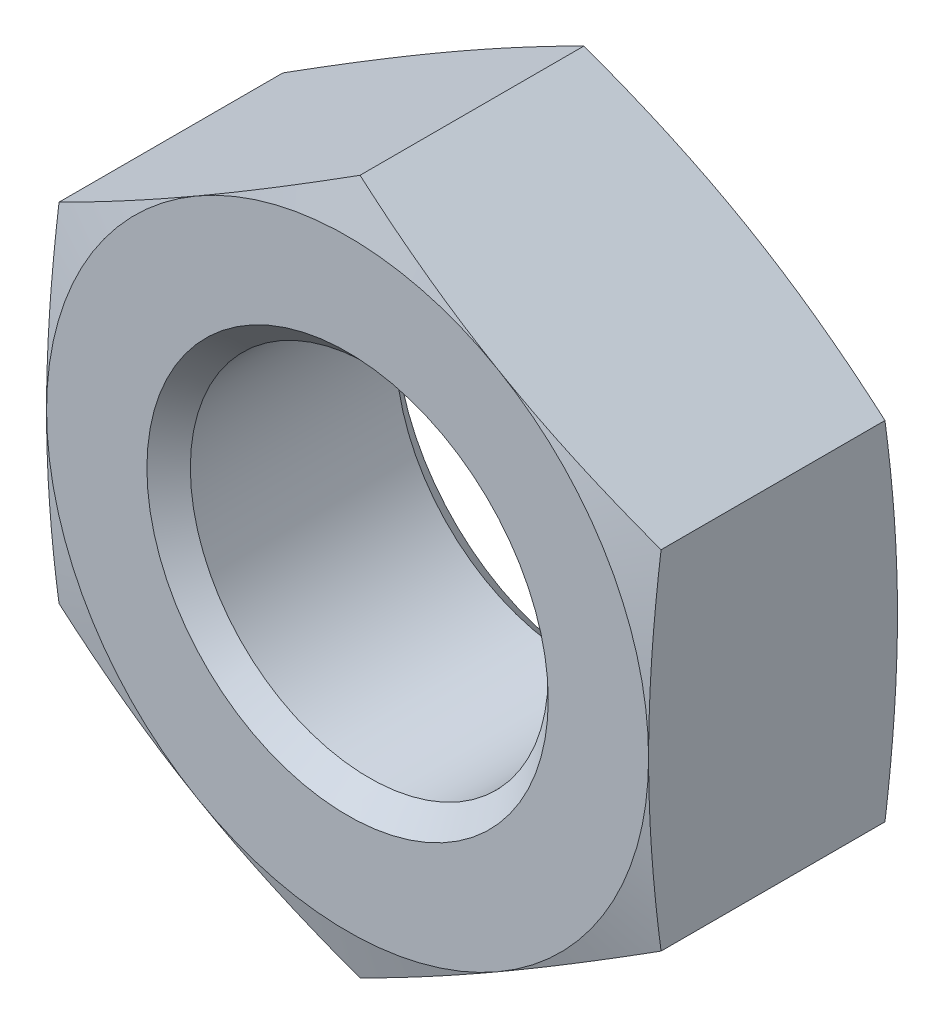
SolidWorks part; units mm, degrees
material "AISI 1045 Steel, cold drawn"
ref_plane "Front Plane" through (0, 0, 0) normal (0, 0, 1) x (1, 0, 0)
ref_plane "Top Plane" through (0, 0, 0) normal (0, 1, 0) x (1, 0, 0)
ref_plane "Right Plane" through (0, 0, 0) normal (1, 0, 0) x (0, 0, -1)
sketch "Sketch1" plane through (0, 0, 0) normal (1, 0, 0) x (0, 0, -1)
  line L0 (0, 0) -> (0, 9.525)
  line L1 (0, 9.525) -> (0.5104, 11.43)
  line L2 (0.5104, 11.43) -> (7.3636, 11.43)
  line L3 (7.3636, 11.43) -> (7.874, 9.525)
  line L4 (7.874, 9.525) -> (7.874, 0)
  line L5 (7.874, 0) -> (0, 0)
  line L6 (7.874, 0) -> (0, 0) construction
sketch "Sketch2" plane through (0, 0, 0) normal (0, 0, 1) x (1, 0, 0)
  line L0 (-19.05, 19.05) -> (-19.05, -19.05)
  line L1 (-19.05, -19.05) -> (19.05, -19.05)
  line L2 (19.05, -19.05) -> (19.05, 19.05)
  line L3 (19.05, 19.05) -> (-19.05, 19.05)
  line L4 (-9.525, 5.4993) -> (-9.525, -5.4993)
  line L5 (-9.525, -5.4993) -> (0, -10.9985)
  line L6 (0, -10.9985) -> (9.525, -5.4993)
  line L7 (9.525, -5.4993) -> (9.525, 5.4993)
  line L8 (9.525, 5.4993) -> (0, 10.9985)
  line L9 (0, 10.9985) -> (-9.525, 5.4993)
revolve "Revolve1" add sketch "Sketch1" angle 360 about L6 reverse direction yes
extrude "Cut-Extrude1" cut sketch "Sketch2" against normal blind 7.874
sketch "Sketch3" plane through (0, 0, 0) normal (1, 0, 0) x (0, 0, -1)
  line L0 (0, 0) -> (0, 6.35)
  line L1 (0, 6.35) -> (0.6871, 5.6629)
  line L2 (0.6871, 5.6629) -> (7.1869, 5.6629)
  line L3 (7.1869, 5.6629) -> (7.874, 6.35)
  line L4 (7.874, 6.35) -> (7.874, 0)
  line L5 (7.874, 0) -> (0, 0)
  line L6 (7.874, 0) -> (0, 0) construction
revolve "Cut-Revolve1" cut sketch "Sketch3" angle 360 about L6 reverse direction yes
cosmetic thread "Cosmetic Thread1" parameters "D1"=7.874, "D2"=12.7
ref_plane "NUT XY" through (0, 0, 0) normal (0, 0, 1) x (1, 0, 0)
ref_plane "NUT XZ" through (0, 0, 0) normal (0, -1, 0) x (-1, 0, 0)
ref_plane "NUT YZ" through (0, 0, 0) normal (1, 0, 0) x (0, 0, -1)
ref_axis "NUT X" through (-80.9, 0, 0) along (1, 0, 0)
ref_axis "NUT Y" through (0, -50, 0) along (0, 1, 0)
ref_axis "NUT Z" through (0, 0, 80.9) along (0, 0, -1)
sketch3d "NUT"
  point P0 (0, 0, 0)
ref_plane "a1 XY" through (0, 0, 0) normal (0, 0, 1) x (1, 0, 0)
ref_plane "a1 XZ" through (0, 9.525, 0) normal (0, -1, 0) x (-1, 0, 0)
ref_plane "a1 YZ" through (-9.525, 0, 0) normal (1, 0, 0) x (0, 0, -1)
ref_axis "a1 X" through (-80.9, 9.525, 0) along (1, 0, 0)
ref_axis "a1 Y" through (-9.525, -50, 0) along (0, 1, 0)
ref_axis "a1 Z" through (-9.525, 9.525, 80.9) along (0, 0, -1)
sketch3d "a1"
  point P0 (-9.525, 9.525, 0)
ref_plane "a2 XY" through (0, 0, 0) normal (0, 0, 1) x (1, 0, 0)
ref_plane "a2 XZ" through (0, 9.525, 0) normal (0, -1, 0) x (-1, 0, 0)
ref_plane "a2 YZ" through (9.525, 0, 0) normal (1, 0, 0) x (0, 0, -1)
ref_axis "a2 X" through (-80.9, 9.525, 0) along (1, 0, 0)
ref_axis "a2 Y" through (9.525, -50, 0) along (0, 1, 0)
ref_axis "a2 Z" through (9.525, 9.525, 80.9) along (0, 0, -1)
sketch3d "a2"
  point P0 (9.525, 9.525, 0)
ref_plane "b1 XY" through (0, 0, 0) normal (1, 0, 0) x (0, 0, -1)
ref_plane "b1 XZ" through (0, 9.525, 0) normal (0, -1, 0) x (-1, 0, 0)
ref_plane "b1 YZ" through (0, 0, 0) normal (0, 0, -1) x (-1, 0, 0)
ref_axis "b1 X" through (0, 9.525, 80.9) along (0, 0, -1)
ref_axis "b1 Y" through (0, -50, 0) along (0, 1, 0)
ref_axis "b1 Z" through (80.9, 9.525, 0) along (-1, 0, 0)
sketch3d "b1"
  point P0 (0, 9.525, 0)
ref_plane "b2 XY" through (0, 0, 0) normal (1, 0, 0) x (0, 0, -1)
ref_plane "b2 XZ" through (0, 9.525, 0) normal (0, -1, 0) x (-1, 0, 0)
ref_plane "b2 YZ" through (0, 0, -7.874) normal (0, 0, -1) x (-1, 0, 0)
ref_axis "b2 X" through (0, 9.525, 80.9) along (0, 0, -1)
ref_axis "b2 Y" through (0, -50, -7.874) along (0, 1, 0)
ref_axis "b2 Z" through (80.9, 9.525, -7.874) along (-1, 0, 0)
sketch3d "b2"
  point P0 (0, 9.525, -7.874)
ref_plane "e XY" through (0, 0, 0) normal (1, 0, 0) x (0, 0, -1)
ref_plane "e XZ" through (0, 0, 0) normal (0, -1, 0) x (-1, 0, 0)
ref_plane "e YZ" through (0, 0, -7.874) normal (0, 0, -1) x (-1, 0, 0)
ref_axis "e X" through (0, 0, 80.9) along (0, 0, -1)
ref_axis "e Y" through (0, -50, -7.874) along (0, 1, 0)
ref_axis "e Z" through (80.9, 0, -7.874) along (-1, 0, 0)
sketch3d "e"
  point P0 (0, 0, -7.874)
ref_plane "ol1 XY" through (0, 0, 0) normal (0, 1, 0) x (1, 0, 0)
ref_plane "ol1 XZ" through (0, 0, -9.525) normal (0, 0, 1) x (1, 0, 0)
ref_plane "ol1 YZ" through (0, 0, 0) normal (1, 0, 0) x (0, 0, -1)
ref_axis "ol1 X" through (-80.9, 0, -9.525) along (1, 0, 0)
ref_axis "ol1 Y" through (0, 0, 50) along (0, 0, -1)
ref_axis "ol1 Z" through (0, 50, -9.525) along (0, -1, 0)
sketch3d "ol1"
  point P0 (0, 0, -9.525)
ref_plane "ol2 XY" through (0, 0, 0) normal (0, 1, 0) x (1, 0, 0)
ref_plane "ol2 XZ" through (0, 0, -9.525) normal (0, 0, 1) x (1, 0, 0)
ref_plane "ol2 YZ" through (7.874, 0, 0) normal (1, 0, 0) x (0, 0, -1)
ref_axis "ol2 X" through (-80.9, 0, -9.525) along (1, 0, 0)
ref_axis "ol2 Y" through (7.874, 0, 50) along (0, 0, -1)
ref_axis "ol2 Z" through (7.874, 50, -9.525) along (0, -1, 0)
sketch3d "ol2"
  point P0 (7.874, 0, -9.525)
ref_plane "th1 XY" through (0, 0, 0) normal (1, 0, 0) x (0, 0, -1)
ref_plane "th1 XZ" through (0, 6.35, 0) normal (0, -1, 0) x (-1, 0, 0)
ref_plane "th1 YZ" through (0, 0, -7.874) normal (0, 0, -1) x (-1, 0, 0)
ref_axis "th1 X" through (0, 6.35, 80.9) along (0, 0, -1)
ref_axis "th1 Y" through (0, -50, -7.874) along (0, 1, 0)
ref_axis "th1 Z" through (80.9, 6.35, -7.874) along (-1, 0, 0)
sketch3d "th1"
  point P0 (0, 6.35, -7.874)
ref_plane "th2 XY" through (0, 0, 0) normal (1, 0, 0) x (0, 0, -1)
ref_plane "th2 XZ" through (0, -6.35, 0) normal (0, -1, 0) x (-1, 0, 0)
ref_plane "th2 YZ" through (0, 0, -7.874) normal (0, 0, -1) x (-1, 0, 0)
ref_axis "th2 X" through (0, -6.35, 80.9) along (0, 0, -1)
ref_axis "th2 Y" through (0, -50, -7.874) along (0, 1, 0)
ref_axis "th2 Z" through (80.9, -6.35, -7.874) along (-1, 0, 0)
sketch3d "th2"
  point P0 (0, -6.35, -7.874)
